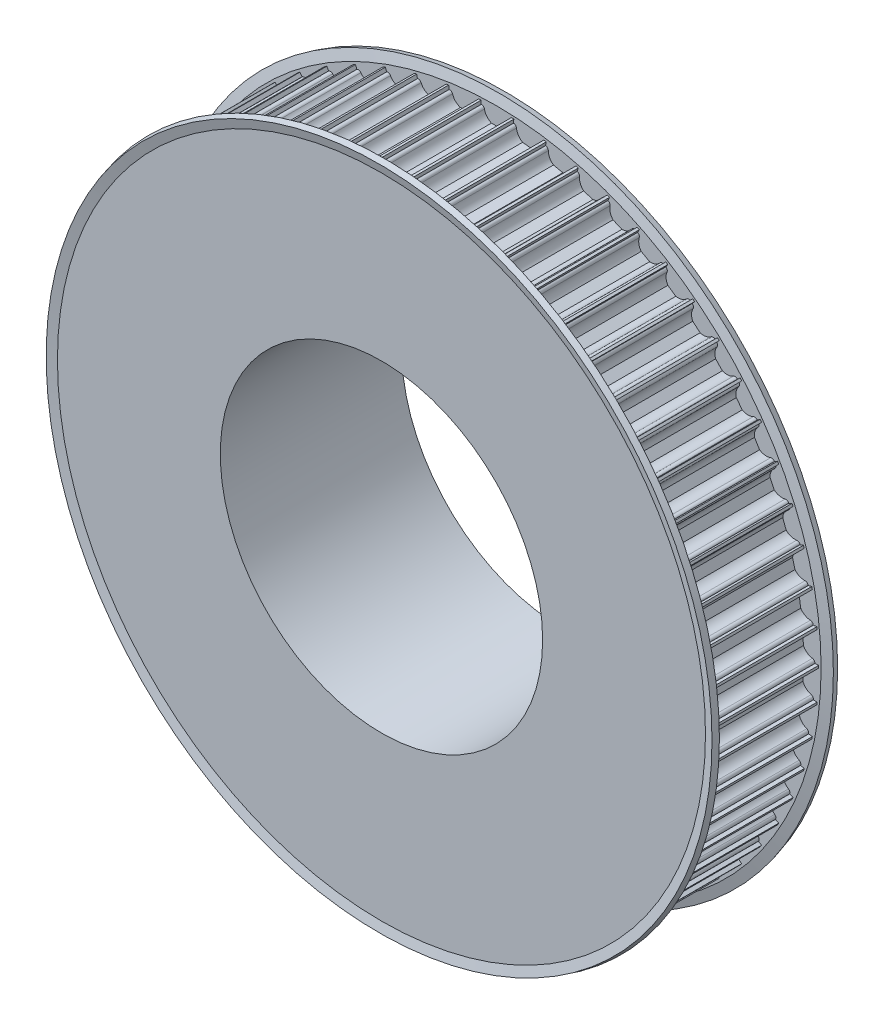
SolidWorks part; units mm, degrees
ref_plane "Front Plane" through (0, 0, 0) normal (0, 0, 1) x (1, 0, 0)
ref_plane "Top Plane" through (0, 0, 0) normal (0, 1, 0) x (1, 0, 0)
ref_plane "Right Plane" through (0, 0, 0) normal (1, 0, 0) x (0, 0, -1)
ref_axis "Axis1" through (0, 0, 101.7273) along (0, 0, -1)
sketch "Sketch1" plane through (0, 0, 0) normal (1, 0, 0) x (0, 0, -1)
  line L0 (0, 40) -> (0, 80)
  line L1 (0, 80) -> (30, 80)
  line L2 (30, 80) -> (30, 55.5)
  line L3 (30, 55.5) -> (45, 55.5)
  line L4 (45, 55.5) -> (45, 40)
  line L5 (45, 40) -> (0, 40)
  line L6 (-101.7273, 0) -> (118.6558, 0) construction
  dimension "D1" = 40
  dimension "D2" = 40
  dimension "D3" = 30
  dimension "D4" = 15
  dimension "D5" = 15.5
revolve "Revolve1" add sketch "Sketch1" angle 360 about axis through (0, 0, 101.7273) along (0, 0, -1)
sketch "Sketch2" plane through (0, 0, 0) normal (0, 0, 1) x (1, 0, 0)
  line L0 (3.6742, 79) -> (3.75, 79)
  line L9 (-3.75, 79) -> (-3.6742, 79)
  line L10 (-3.75, 79) -> (-3.75, 81)
  line L11 (-3.75, 81) -> (3.75, 81)
  line L12 (3.75, 79) -> (3.75, 81)
  line L13 (-1.199, 76.25) -> (1.199, 76.25)
  arc A0 (-2.9394, 78.4) -> (-1.199, 76.25) centre (0, 79) ccw
  arc A1 (-2.9394, 78.4) -> (-3.6742, 79) centre (-3.6742, 78.25) ccw
  arc A2 (3.6742, 79) -> (2.9394, 78.4) centre (3.6742, 78.25) ccw
  arc A3 (1.199, 76.25) -> (2.9394, 78.4) centre (0, 79) ccw
  dimension "D1" = 2
  dimension "D2" = 7.5
  dimension "D3" = 3
  dimension "D5" = 0.75
  dimension "D6" = 0.75
  dimension "D8" = 4.75
  dimension "D4" = 79
  dimension "D7" = 2.75
extrude "Cut-Extrude1" cut sketch "Sketch2" against normal through all
pattern_circular "CirPattern1" count 62 over 360 about axis through (0, 0, 101.7273) along (0, 0, -1) of "Cut-Extrude1"
sketch "Sketch3" plane through (0, 0, 0) normal (1, 0, 0) x (0, 0, -1)
  line L0 (1.5, 80.6121) -> (0.0511, 80.2238) construction
  line L1 (0, 80.6121) -> (1.5, 80.6121) construction
  line L2 (0, 80.6121) -> (0, 75.6121)
  line L3 (0, 75.6121) -> (1.5, 75.6121)
  line L4 (1.5, 80.6121) -> (1.5, 75.6121)
  line L5 (1.5, 80.6121) -> (0.8569, 83.0121)
  line L6 (0.0511, 80.2238) -> (-0.592, 82.6238)
  line L7 (0.8569, 83.0121) -> (-0.592, 82.6238)
  line L8 (0, 78.2951) -> (0, 75.9801) construction
  line L9 (30, 79.9121) -> (0, 79.9121) construction
  line L10 (15, 36.1946) -> (15, -38.4551) construction
  line L11 (30, 80.6121) -> (28.5, 80.6121) construction
  line L12 (29.1431, 83.0121) -> (30.592, 82.6238)
  line L13 (29.9489, 80.2238) -> (30.592, 82.6238)
  line L14 (28.5, 80.6121) -> (29.1431, 83.0121)
  line L15 (28.5, 80.6121) -> (28.5, 75.6121)
  line L16 (30, 75.6121) -> (28.5, 75.6121)
  line L17 (30, 80.6121) -> (30, 75.6121)
  line L18 (28.5, 80.6121) -> (29.9489, 80.2238) construction
  dimension "D1" = 1.5
  dimension "D2" = 5
  dimension "D3" = 1.5
  dimension "D4" = 2.4
  dimension "D5" = 165
  dimension "D6" = 0.7
revolve "Revolve2" add sketch "Sketch3" angle 360 about axis through (0, 0, 101.7273) along (0, 0, -1) region at (0, 79.2432, -0.6556)
revolve "Revolve3" add sketch "Sketch3<4>" angle 360 about axis through (0, 0, 101.7273) along (0, 0, -1) region at (0, 79.2432, -29.3444)
sketch "Sketch3<4>" plane through (0, 0, 0) normal (1, 0, 0) x (0, 0, -1) same geometry as "Sketch3"
